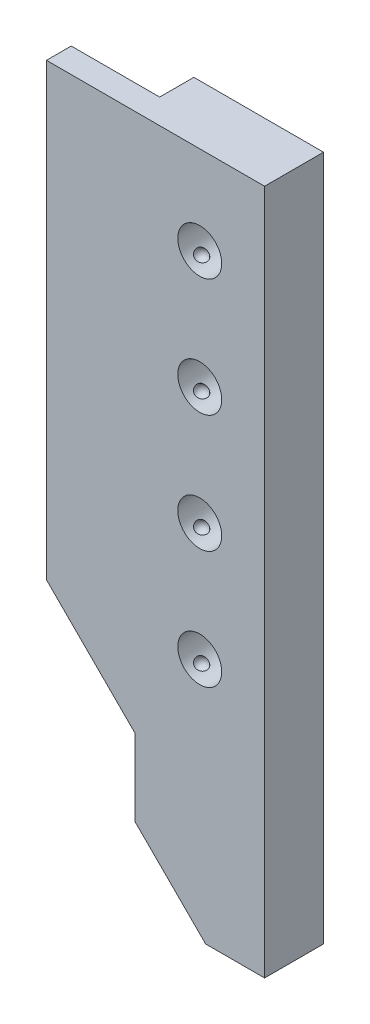
SolidWorks part; units mm, degrees
ref_plane "Front Plane" through (0, 0, 0) normal (0, 0, 1) x (1, 0, 0)
ref_plane "Top Plane" through (0, 0, 0) normal (0, 1, 0) x (1, 0, 0)
ref_plane "Right Plane" through (0, 0, 0) normal (1, 0, 0) x (0, 0, -1)
sketch "Sketch1" plane through (0, 0, 0) normal (0, 0, 1) x (1, 0, 0)
  line L0 (25.2, 31.3209) -> (25.2, -45)
  line L1 (25.2, -45) -> (40.2, -60)
  line L2 (40.2, -60) -> (40.2, 0) construction
  line L3 (40.2, -60) -> (40.2, -85)
  line L5 (62.2, -85) -> (62.2, 31.3209)
  line L6 (62.2, 31.3209) -> (25.2, 31.3209)
  line L12 (40.2, -85) -> (62.2, -85)
  line L13 (40.2, -60) -> (40.2, 31.3209)
  circle A0 centre (0, 0) radius 40.2 construction
  dimension "D1" = 80.4
  dimension "D2" = 15
  dimension "D3" = 15
  dimension "D4" = 60
  dimension "D5" = 25
  dimension "D6" = 22
extrude "Boss-Extrude1" add sketch "Sketch1" along normal blind 4.2 contours L1 L13 L6 L0 | L13 L3 L12 L5 L6 region at (32.9237, -10.7014, 0) region at (51.2, -26.8395, 0)
extrude "Boss-Extrude2" add sketch "Sketch1<3>" against normal blind 5.8 contours L13 L3 L12 L5 L6 region at (51.2, -26.8395, 0)
sketch "Sketch1<3>" plane through (0, 0, 0) normal (0, 0, 1) x (1, 0, 0) same geometry as "Sketch1"
sketch "Sketch2" plane through (0, 0, 4.2) normal (0, 0, 1) x (1, 0, 0)
  line L1 (40.2, -85) -> (62.2, -85) construction
  line L2 (62.2, 31.3209) -> (25.2, 31.3209) construction
  circle A0 centre (51.2, 16.3209) radius 3.725
  point P5 (51.2, -85)
  dimension "D1" = 7.45
  dimension "D2" = 15
extrude "Cut-Extrude1" cut sketch "Sketch2" against normal up to next
ref_axis "Axis1" through (51.2, 16.3209, -5.8) along (0, 0, 1)
ref_plane "Plane1" through (51.2, 0, 0) normal (-1, 0, 0) x (0, 0, 1)
sketch "Sketch3" plane through (51.2, 0, 0) normal (-1, 0, 0) x (0, 0, 1)
  line L0 (4.2, 31.3209) -> (4.2, -45) construction
  line L1 (-5.8, -85) -> (-5.8, 31.3209) construction
  circle A0 centre (-3.8, 20.2459) radius 0.65
  circle A1 centre (2.2, 20.2459) radius 0.65
  dimension "D1" = 1.3
  dimension "D3" = 2
  dimension "D4" = 2
  dimension "D2" = 0.2
pattern_linear "LPattern1" count 4 spacing 20 along (0, -1, 0) of "Cut-Extrude1"
sketch "Sketch4" plane through (0, 0, 4.2) normal (0, 0, 1) x (1, 0, 0)
  line L0 (52.2, -85) -> (40.2, -73)
  line L1 (40.2, -85) -> (62.2, -85) construction
  line L2 (40.2, -85) -> (40.2, -60) construction
  line L3 (40.2, -73) -> (40.2, -85)
  line L4 (40.2, -85) -> (52.2, -85)
  dimension "D1" = 10
  dimension "D2" = 45
extrude "Cut-Extrude2" cut sketch "Sketch4" against normal up to next
ref_plane "Plane2" through (25.2, -45, 0) normal (0, -1, 0) x (-1, 0, 0)
sketch "Sketch6" plane through (25.2, 0, 0) normal (-1, 0, 0) x (0, 0, 1)
  line L0 (4.2, -45) -> (0, -45)
  line L1 (-20.9883, -45) -> (20.9883, -45) construction
  line L2 (4.2, -45) -> (4.2, -60) construction
  line L3 (0, -45) -> (3.7, -60)
  line L4 (4.2, -60) -> (0, -60) construction
  line L5 (3.7, -60) -> (4.2, -60)
  line L6 (4.2, -60) -> (4.2, -45)
  line L8 (4.2, -45) -> (0, -45)
  line L9 (4.2, -45) -> (4.2, -60)
  line L10 (4.2, -60) -> (0, -60)
  line L11 (0, -45) -> (0, -60)
  dimension "D1" = 0.5
extrude "Cut-Extrude3" cut sketch "Sketch6" against normal up to surface (15 mm away) contours L3 L11 L10 region at (25.2, -55, 1.2333) up to face at (40.2, -33.893, -0.5333)
ref_plane "Plane3" through (25.5117, -18.7086, 0) normal (0.8064, -0.5914, 0) x (0, 0, -1)
sketch "Sketch9" plane through (25.5117, -18.7086, 0) normal (0.8064, -0.5914, 0) x (0, 0, -1)
  line L1 (-2.8, 47.1641) -> (-0.6, 47.1641) construction
  line L2 (5.8, 47.1641) -> (-4.2, 47.1641) construction
  line L3 (-4.2, -31.7616) -> (-4.2, 62.0402) construction
  line L5 (-2.9, 47.6437) -> (-0.5, 47.6437) construction
  line L6 (-0.5, 47.6437) -> (-2.9, 47.6437)
  arc A0 (-2.9, 47.6437) -> (-0.5, 47.6437) centre (-1.7, 47.6437) ccw
  point P11 (-1.7, 47.6437)
  dimension "D1" = 2.4
  dimension "D2" = 2.2
  dimension "D3" = 2.5
revolve "Cut-Revolve4" cut sketch "Sketch9" angle 360 about L6
pattern_circular "CirPattern1" count 4 over 360 about axis through (51.2, 16.3209, -5.8) along (0, 0, 1) of "Cut-Revolve4"
pattern_linear "LPattern2" count 4 spacing 20 along (0, -1, 0) count 2 spacing 5 along (0, 0, -1) of "Cut-Revolve4", "CirPattern1"
